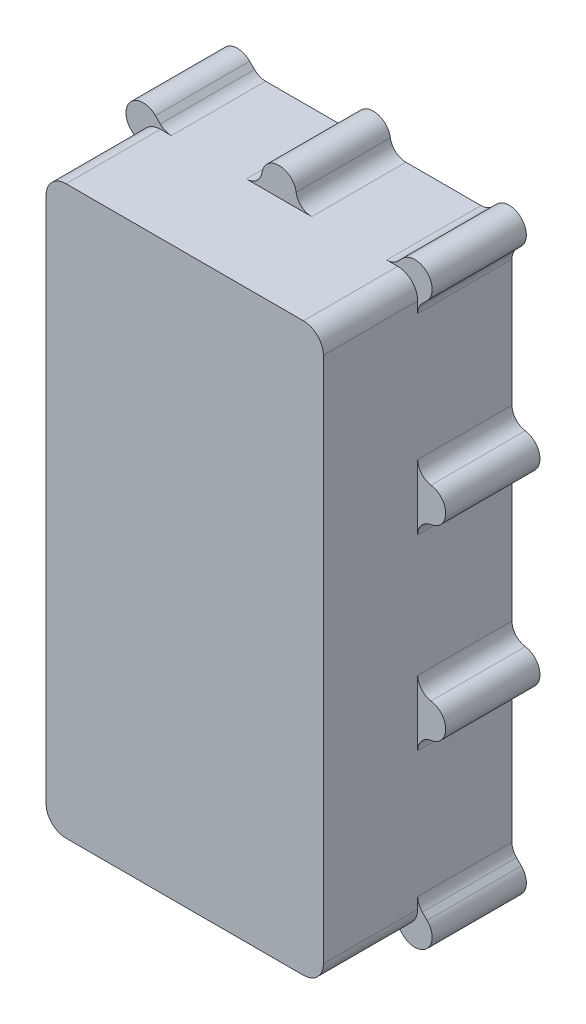
SolidWorks part; units mm, degrees
material "ABS"
ref_plane "X-Y Datum" through (0, 0, 0) normal (0, 0, 1) x (1, 0, 0)
ref_plane "X-Z Datum" through (0, 0, 0) normal (0, 1, 0) x (1, 0, 0)
ref_plane "Y-Z Datum" through (0, 0, 0) normal (1, 0, 0) x (0, 0, -1)
sketch "Sketch1" plane through (0, 0, 0) normal (0, 0, 1) x (1, 0, 0)
  line L0 (1.8162, 48.1563) -> (125.4513, 48.1563) construction
  line L1 (24.3593, 48.1563) -> (24.3593, 120.2923) construction
  line L3 (24.3593, 120.2923) -> (125.4513, 120.2923) construction
  line L8 (125.4513, 48.1563) -> (125.4513, 120.2923) construction
  line L33 (24.3593, 120.2923) -> (1.8162, 120.2923) construction
  line L34 (24.3593, 120.2923) -> (24.3593, 48.1563) construction
  line L35 (63.6337, 48.1563) -> (63.6337, 43.0763) construction
  line L36 (1.8162, 120.2923) -> (1.8162, 48.1563) construction
  line L41 (24.3593, 120.2923) -> (23.7243, 120.2923) construction
  line L42 (24.3593, 120.2923) -> (24.3593, 122.8323) construction
  line L44 (27.5343, 14.7553) -> (27.5343, 43.0763) construction
  line L45 (125.4513, 120.2923) -> (127.9913, 120.2923) construction
  line L46 (27.5343, 14.7553) -> (125.4513, 14.7553) construction
  line L47 (23.7243, 122.8323) -> (127.9913, 122.8323)
  line L48 (23.7243, 122.8323) -> (23.7243, -21.9477)
  line L49 (23.7243, -21.9477) -> (127.9913, -21.9477)
  line L50 (127.9913, 122.8323) -> (127.9913, -21.9477)
  line L51 (125.4513, 14.7553) -> (125.4513, 43.0763) construction
  line L52 (27.5343, 43.0763) -> (125.4513, 43.0763) construction
  line L53 (23.7243, 120.2923) -> (23.7243, 48.1563) construction
  circle A17 centre (30.4553, 114.1963) radius 2.1 construction
  circle A18 centre (119.8633, 115.2123) radius 2.1 construction
  circle A19 centre (119.6813, 54.2533) radius 2.1 construction
  circle A20 centre (29.4393, 53.2363) radius 2.1 construction
  circle A26 centre (31.9793, 18.4383) radius 2.1 construction
  circle A27 centre (31.9793, 39.3933) radius 2.1 construction
  circle A28 centre (120.6193, 28.8183) radius 2.1 construction
sketch "Sketch2" plane through (0, 0, 0) normal (0, 0, 1) x (1, 0, 0)
  line L4 (55.176, 122.8323) -> (127.9913, 122.8323)
  line L6 (55.176, 48.5244) -> (55.176, 50.9244) construction
  line L7 (55.176, -21.05) -> (127.9913, -21.05)
  line L8 (127.9913, 122.8323) -> (127.9913, -21.05)
  line L9 (55.176, 110.2103) -> (127.9913, -21.05) construction
  line L10 (55.176, -8.428) -> (127.9913, 122.8323) construction
  line L11 (55.176, 50.9244) -> (55.176, -21.05)
  line L12 (55.176, 50.9244) -> (55.176, 122.8323)
  circle A7 centre (88.0827, 6.45) radius 27.5
  circle A8 centre (88.0294, 95.3501) radius 27.5
  circle A9 centre (98.216, 50.8911) radius 6.477
  circle A10 centre (77.896, 50.9089) radius 6.477
  circle A11 centre (121.5143, 31.8208) radius 6.477
  circle A12 centre (115.996, 50.8756) radius 2.4
  circle A13 centre (55.176, 50.9244) radius 2.4
  point P14 (88.0827, 50.8911)
sketch "Sketch3" plane through (0, 0, 0) normal (0, 0, 1) x (1, 0, 0)
  line L7 (0, 0) -> (76.2, 0)
  line L10 (0, 0) -> (0, 168.275)
  line L11 (0, 168.275) -> (76.2, 168.275)
  line L12 (76.2, 0) -> (76.2, 168.275)
  dimension "D1" = 168.275
  dimension "D2" = 76.2
extrude "Boss-Extrude1" add sketch "Sketch3" along normal blind 53.975
shell "Shell1" thickness 6 removed face at (38.1, 84.1375, 0) outward yes
fillet "Fillet1" radius 5.334 4 edges at (76.2, 168.275, 26.9875) (76.2, 0, 26.9875) (0, 0, 26.9875) (0, 168.275, 26.9875)
fillet "Fillet2" radius 6.35 4 edges at (-6, -6, 29.9875) (-6, 174.275, 29.9875) (82.2, 174.275, 29.9875) (82.2, -6, 29.9875)
sketch "Sketch6" plane through (0, 0, 0) normal (0, 0, -1) x (-1, 0, 0)
  line L8 (-5.334, 172.5577) -> (-70.866, 172.5577)
  line L9 (-80.4827, 162.941) -> (-80.4827, 5.334)
  line L10 (-70.866, -4.2827) -> (-5.334, -4.2827)
  line L11 (4.2827, 5.334) -> (4.2827, 162.941)
  line L12 (-79.2, 162.941) -> (-79.2, 5.334)
  line L13 (-70.866, -3) -> (-5.334, -3)
  line L14 (3, 5.334) -> (3, 162.941)
  line L15 (-5.334, 171.275) -> (-70.866, 171.275)
  line L16 (-79.2, 162.941) -> (-79.2, 5.334) construction
  line L17 (-70.866, -3) -> (-5.334, -3) construction
  line L18 (3, 5.334) -> (3, 162.941) construction
  line L19 (-5.334, 171.275) -> (-70.866, 171.275) construction
  line L20 (-77.9173, 162.941) -> (-77.9173, 5.334)
  line L21 (-70.866, -1.7173) -> (-5.334, -1.7173)
  line L22 (1.7173, 5.334) -> (1.7173, 162.941)
  line L23 (-5.334, 169.9923) -> (-70.866, 169.9923)
  arc A8 (-70.866, 172.5577) -> (-80.4827, 162.941) centre (-70.866, 162.941) ccw
  arc A9 (-80.4827, 5.334) -> (-70.866, -4.2827) centre (-70.866, 5.334) ccw
  arc A10 (-5.334, -4.2827) -> (4.2827, 5.334) centre (-5.334, 5.334) ccw
  arc A11 (4.2827, 162.941) -> (-5.334, 172.5577) centre (-5.334, 162.941) ccw
  arc A12 (-70.866, 171.275) -> (-79.2, 162.941) centre (-70.866, 162.941) ccw
  arc A13 (-79.2, 5.334) -> (-70.866, -3) centre (-70.866, 5.334) ccw
  arc A14 (-5.334, -3) -> (3, 5.334) centre (-5.334, 5.334) ccw
  arc A15 (3, 162.941) -> (-5.334, 171.275) centre (-5.334, 162.941) ccw
  arc A16 (-70.866, 171.275) -> (-79.2, 162.941) centre (-70.866, 162.941) ccw construction
  arc A17 (-79.2, 5.334) -> (-70.866, -3) centre (-70.866, 5.334) ccw construction
  arc A18 (-5.334, -3) -> (3, 5.334) centre (-5.334, 5.334) ccw construction
  arc A19 (3, 162.941) -> (-5.334, 171.275) centre (-5.334, 162.941) ccw construction
  arc A20 (-77.9173, 5.334) -> (-70.866, -1.7173) centre (-70.866, 5.334) ccw
  arc A21 (-5.334, -1.7173) -> (1.7173, 5.334) centre (-5.334, 5.334) ccw
  arc A22 (1.7173, 162.941) -> (-5.334, 169.9923) centre (-5.334, 162.941) ccw
  arc A23 (-70.866, 169.9923) -> (-77.9173, 162.941) centre (-70.866, 162.941) ccw
  dimension "D4" = 7.0513
  dimension "D5" = 2.5654
  dimension "D1" = 3
  dimension "D2" = 1.2827
  dimension "D3" = 1.2827
extrude "Cut-Extrude1" cut sketch "Sketch6" against normal blind 1.2446
fillet "Fillet3" radius 0.254 16 edges at (-4.2827, 84.1375, 1.2446) (-1.466, -1.466, 1.2446) (38.1, -4.2827, 1.2446) (77.666, -1.466, 1.2446) (80.4827, 84.1375, 1.2446) (77.666, 169.741, 1.2446) (38.1, 172.5577, 1.2446) (-1.466, 169.741, 1.2446) (75.852, 167.927, 1.2446) (77.9173, 84.1375, 1.2446) (75.852, 0.348, 1.2446) (38.1, -1.7173, 1.2446) (0.348, 0.348, 1.2446) (-1.7173, 84.1375, 1.2446) (0.348, 167.927, 1.2446) (38.1, 169.9923, 1.2446)
fillet "Fillet4" radius 0.127 16 edges at (75.852, 167.927, 0) (38.1, 169.9923, 0) (0.348, 167.927, 0) (-1.7173, 84.1375, 0) (0.348, 0.348, 0) (38.1, -1.7173, 0) (75.852, 0.348, 0) (77.666, 169.741, 0) (38.1, 172.5577, 0) (-1.466, 169.741, 0) (-4.2827, 84.1375, 0) (-1.466, -1.466, 0) (38.1, -4.2827, 0) (77.666, -1.466, 0) (77.9173, 84.1375, 0) (80.4827, 84.1375, 0)
sketch "Sketch7" plane through (0, 0, 53.975) normal (0, 0, -1) x (-1, 0, 0)
  line L0 (-76.2, 32) -> (0, 32)
  line L1 (-76.2, 5.334) -> (-76.2, 162.941) construction
  line L2 (0, 162.941) -> (0, 5.334) construction
  line L3 (-76.2, 34.5) -> (0, 34.5)
  line L4 (-5.334, 0) -> (-70.866, 0) construction
  line L5 (-76.2, 32) -> (-76.2, 34.5)
  line L6 (0, 32) -> (0, 34.5)
  dimension "D2" = 32
  dimension "D1" = 2.5
extrude "Boss-Extrude2" add sketch "Sketch7" along normal up to surface (53.975 mm away) up to face at (38.1, 84.1375, 0)
sketch "Sketch8" plane through (0, 0, 0) normal (0, 0, -1) x (-1, 0, 0)
  line L0 (-5.334, 5.334) -> (5.0914, -5.0914)
  line L1 (-1.7782, -6) -> (1.2023, -8.9805)
  line L2 (-0.35, -6) -> (-75.85, -6) construction
  line L3 (-5.334, -4.2827) -> (-5.334, -4.4097)
  line L4 (4.4097, 5.334) -> (4.2827, 5.334)
  line L5 (-5.334, -4.2827) -> (-5.334, -4.4097)
  line L6 (4.4097, 5.334) -> (4.2827, 5.334)
  line L7 (6, 1.7782) -> (8.9805, -1.2023)
  line L8 (6, 167.925) -> (6, 0.35) construction
  line L9 (-38.1, -6) -> (-38.1, 174.275) construction
  line L10 (-75.85, 174.275) -> (-0.35, 174.275) construction
  line L11 (-82.2, 84.1375) -> (6, 84.1375) construction
  line L12 (-82.2, 0.35) -> (-82.2, 167.925) construction
  circle A0 centre (5.0914, -5.0914) radius 3.025
  circle A1 centre (5.0914, -5.0914) radius 5.5
  arc A3 (-5.334, -4.4097) -> (4.4097, 5.334) centre (-5.334, 5.334) ccw
  arc A4 (-5.334, -4.2827) -> (4.2827, 5.334) centre (-5.334, 5.334) ccw
  arc A5 (-5.334, -4.4097) -> (4.4097, 5.334) centre (-5.334, 5.334) ccw
  arc A6 (-5.334, -4.2827) -> (4.2827, 5.334) centre (-5.334, 5.334) ccw
  point P6 (1.5558, -1.5558)
  arc M11 (4.4097, 5.334) -> (-5.334, -4.4097) centre (-5.334, 5.334) cw
  line M14 (-75.85, -6) -> (-0.35, -6)
  arc M15 (-0.35, -6) -> (6, 0.35) centre (-0.35, 0.35) ccw
  line M16 (6, 0.35) -> (6, 167.925)
  dimension "D1" = 6.05
  dimension "D4" = 11
  dimension "D3" = 5
  dimension "D2" = 0
extrude "Boss-Extrude3" add sketch "Sketch8" against normal blind 29.972 contours A1 A0 M15 | A1 L1 M15 M14 | A1 L7 M16 M15 | A0 M15 | L0 A0 M15 | A0 L0 M15 | A1 A0 L0 M11 M15 | A1 L0 A0 M15 M11 region at (-3.9532, -1.0787, 0) region at (-1.0787, -3.9532, 0) region at (-4.2457, -2.9327, 0) region at (-2.9327, -4.2457, 0) region at (-6.789, 0.5448, 0) region at (-7.5393, -0.3393, 0) region at (0.5448, -6.789, 0) region at (-5.4552, -5.4552, 0)
sketch "Sketch9" plane through (0, 0, 0) normal (0, 0, -1) x (-1, 0, 0)
  circle A0 centre (5.0914, -5.0914) radius 3.025 construction
  circle A1 centre (5.0914, -5.0914) radius 3.025
  dimension "D1" = 6.05
extrude "Cut-Extrude2" cut sketch "Sketch9" against normal blind 9
ref_plane "Plane1" through (38.1, 0, 0) normal (-1, 0, 0) x (0, 0, 1)
ref_plane "Plane2" through (0, 84.1375, 0) normal (0, -1, 0) x (-1, 0, 0)
mirror "Mirror1" about plane through (38.1, 0, 0) normal (-1, 0, 0) of "Cut-Extrude2", "Boss-Extrude3"
mirror "Mirror2" about plane through (0, 84.1375, 0) normal (0, -1, 0) of "Cut-Extrude2", "Boss-Extrude3", "Mirror1"
sketch "Sketch10" plane through (0, 0, 0) normal (0, 0, -1) x (-1, 0, 0)
  line L0 (6, 84.1375) -> (39.3327, 84.1375) construction
  line L2 (6, 166.4968) -> (6, 1.7782) construction
  line L3 (6, 84.1375) -> (6, 157.4914)
  line L4 (6, 113.8555) -> (9.4097, 113.8555) construction
  line L5 (4.4097, 162.941) -> (4.4097, 5.334) construction
  line L7 (9.4097, 119.3555) -> (6, 119.3555)
  line L9 (9.4097, 108.3555) -> (6, 108.3555)
  line L10 (9.4097, 48.9195) -> (6, 48.9195)
  line L11 (9.4097, 59.9195) -> (6, 59.9195)
  circle A4 centre (9.4097, 113.8555) radius 3.025
  circle A5 centre (9.4097, 113.8555) radius 5.5
  circle A6 centre (9.4097, 54.4195) radius 3.025
  circle A7 centre (9.4097, 54.4195) radius 5.5
  point P0 (5.0914, 173.3664)
  point P1 (5.0914, -5.0914)
  point P3 (-81.2914, -5.0914)
  line M14 (6, 1.7782) -> (6, 166.4968)
  line M21 (4.4097, 162.941) -> (4.4097, 5.334)
  dimension "D3" = 89.2289
  dimension "D4" = 6.05
  dimension "D5" = 11
  dimension "D1" = 178.4577
  dimension "D2" = 86.3827
  dimension "D6" = 5
  dimension "D7" = 29.718
  dimension "D8" = 59.5109
  dimension "D9" = 59.436
  dimension "D10" = 59.5109
extrude "Boss-Extrude4" add sketch "Sketch10" against normal blind 29.972 contours A7 A6 M14 | A7 L11 M14 | A7 M14 M21 | L10 A7 M14 | A6 | A5 L7 L3 | A5 L3 L9 | A5 A4 M14 | A5 M14 M21 | A4 region at (-6.833, 108.7032, 0) region at (-6.833, 59.5718, 0) region at (-5.2799, 113.8555, 0) region at (-6.1416, 113.8555, 0) region at (-13.1987, 58.2085, 0) region at (-5.2799, 54.4195, 0) region at (-6.833, 119.0078, 0) region at (-6.833, 49.2672, 0) region at (-9.4097, 113.8555, 0) region at (-9.4097, 54.4195, 0)
sketch "Sketch11" plane through (0, 0, 0) normal (0, 0, -1) x (-1, 0, 0)
  circle A0 centre (9.4097, 54.4195) radius 3.025 construction
  circle A1 centre (9.4097, 113.8555) radius 3.025 construction
  circle A2 centre (9.4097, 54.4195) radius 3.025
  circle A3 centre (9.4097, 113.8555) radius 3.025
  dimension "D1" = 6.05
extrude "Cut-Extrude3" cut sketch "Sketch11" against normal blind 9
mirror "Mirror3" about plane through (38.1, 0, 0) normal (-1, 0, 0) of "Cut-Extrude3", "Boss-Extrude4"
sketch "Sketch12" plane through (0, 0, 0) normal (0, 0, -1) x (-1, 0, 0)
  line L0 (-74.4218, -6) -> (-1.7782, -6)
  line L1 (-38.1, -6) -> (-38.1, -9.4097) construction
  line L2 (-5.334, -4.4097) -> (-70.866, -4.4097) construction
  line L3 (-43.6, -9.4097) -> (-43.6, -6)
  line L4 (-32.6, -9.4097) -> (-32.6, -6)
  circle A0 centre (-38.1, -9.4097) radius 3.025
  circle A1 centre (-38.1, -9.4097) radius 5.5
  point P15 (-81.2914, -5.0914)
  point P16 (5.0914, -5.0914)
  line M16 (-74.4218, -6) -> (-1.7782, -6)
  line M42 (-5.334, -4.4097) -> (-70.866, -4.4097)
  dimension "D2" = 6.05
  dimension "D4" = 11
  dimension "D1" = 43.1914
  dimension "D3" = 5
  dimension "D5" = 86.3827
extrude "Boss-Extrude5" add sketch "Sketch12" against normal blind 29.972 contours A1 L0 A0 M16 | A1 L0 L3 | A1 L4 L0 | A0 | L0 A1 M16 M42 region at (43.2523, -6.833, 0) region at (38.1, -5.2799, 0) region at (38.1, -6.1416, 0) region at (32.9477, -6.833, 0) region at (38.1, -9.4097, 0)
sketch "Sketch13" plane through (0, 0, 0) normal (0, 0, -1) x (-1, 0, 0)
  circle A0 centre (-38.1, -9.4097) radius 3.025 construction
  circle A1 centre (-38.1, -9.4097) radius 3.025
extrude "Cut-Extrude4" cut sketch "Sketch13" against normal blind 9
mirror "Mirror4" about plane through (0, 84.1375, 0) normal (0, -1, 0) of "Cut-Extrude4", "Boss-Extrude5"
sketch "Sketch17" plane through (-6, 0, 0) normal (-1, 0, 0) x (0, 0, 1)
  line L0 (59.975, 167.925) -> (59.975, 0.35) construction
  line L1 (0, 34.5) -> (53.975, 34.5) construction
  line L2 (53.975, 32) -> (53.975, 5.334) construction
  circle A0 centre (38.385, 85.3) radius 9.525
  circle A1 centre (38.385, 85.3) radius 14.2875
  circle A2 centre (38.385, 18.667) radius 6.35
  circle A3 centre (38.385, 18.667) radius 10.795
  point P10 (53.975, 18.667)
  dimension "D1" = 19.05
  dimension "D4" = 28.575
  dimension "D5" = 12.7
  dimension "D6" = 21.59
  dimension "D2" = 21.59
  dimension "D3" = 50.8
extrude "Cut-Extrude6" cut sketch "Sketch17" against normal blind 6 contours A0 | A2 region at (-6, 85.3, 38.385) region at (-6, 18.667, 38.385)
sketch "Sketch18" plane through (0, 0, 0) normal (1, 0, 0) x (0, 0, -1)
  circle A0 centre (-38.385, 85.3) radius 14.2875 construction
  circle A1 centre (-38.385, 85.3) radius 14.2875
  circle A2 centre (-38.385, 18.667) radius 10.795 construction
  circle A3 centre (-38.385, 18.667) radius 10.795
extrude "Cut-Extrude7" cut sketch "Sketch18" against normal blind 3
fillet "Fillet5" radius 5 20 edges at (1.7782, -6, 14.986) (-6, 1.7782, 14.986) (32.6, -6, 14.986) (43.6, -6, 14.986) (74.4218, -6, 14.986) (82.2, 1.7782, 14.986) (82.2, 48.9195, 14.986) (82.2, 59.9195, 14.986) (82.2, 108.3555, 14.986) (82.2, 119.3555, 14.986) (82.2, 166.4968, 14.986) (74.4218, 174.275, 14.986) (43.6, 174.275, 14.986) (32.6, 174.275, 14.986) (1.7782, 174.275, 14.986) (-6, 166.4968, 14.986) (-6, 108.3555, 14.986) (-6, 119.3555, 14.986) (-6, 59.9195, 14.986) (-6, 48.9195, 14.986)
